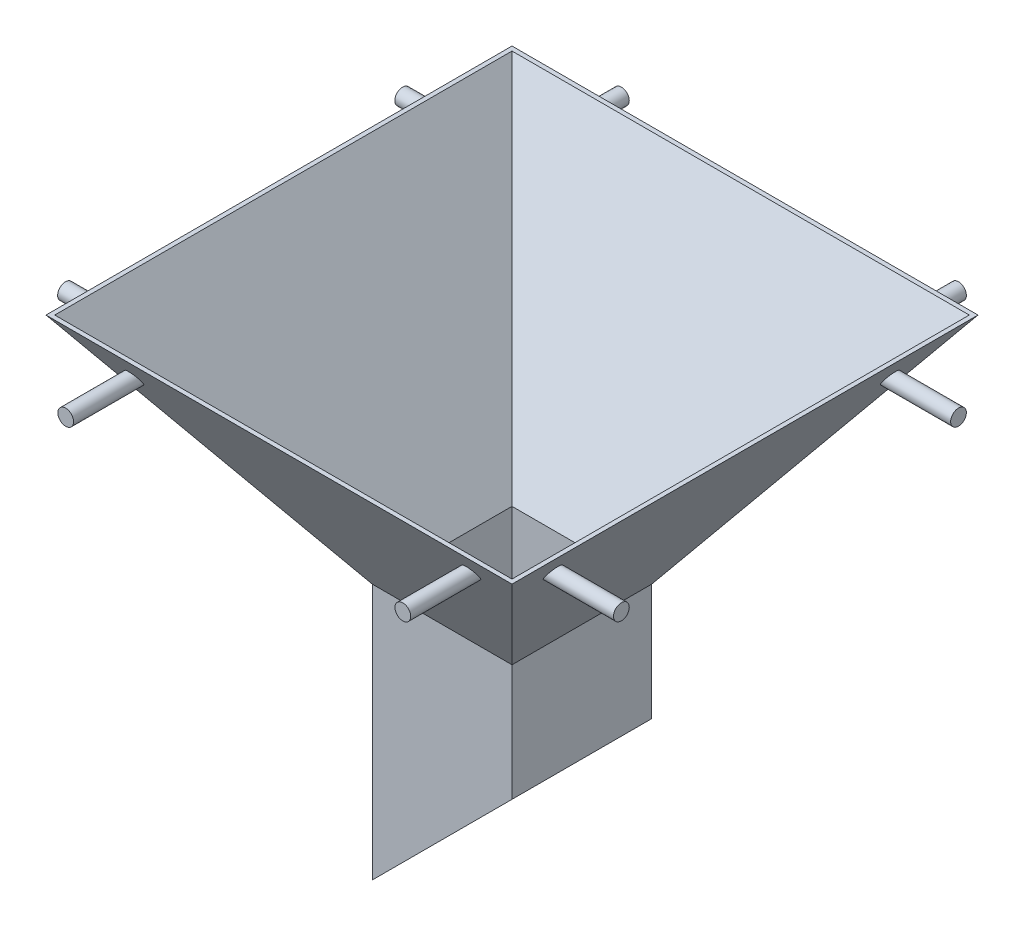
SolidWorks part; units mm, degrees
ref_plane "Alzado" through (0, 0, 0) normal (0, 0, 1) x (1, 0, 0)
ref_plane "Planta" through (0, 0, 0) normal (0, 1, 0) x (1, 0, 0)
ref_plane "Vista lateral" through (0, 0, 0) normal (1, 0, 0) x (0, 0, -1)
sketch "Croquis2" plane through (0, 0, 0) normal (0, 1, 0) x (1, 0, 0)
  line L1 (0, 0) -> (414.7, 0)
  line L2 (0, 0) -> (0, 414.7)
  line L3 (0, 414.7) -> (414.7, 414.7)
  line L4 (414.7, 0) -> (414.7, 414.7)
  dimension "D1" = 414.7
ref_plane "Plano1" through (0, -207.4, 0) normal (0, 1, 0) x (1, 0, 0)
sketch "Croquis3" plane through (0, -207.4, 0) normal (0, 1, 0) x (1, 0, 0)
  line L0 (207.35, 414.7) -> (207.35, 0) construction
  line L1 (0, 414.7) -> (414.7, 414.7) construction
  line L2 (0, 0) -> (414.7, 0) construction
  line L3 (207.35, 0) -> (414.7, 207.35) construction
  line L4 (414.7, 0) -> (414.7, 414.7) construction
  line L5 (414.7, 207.35) -> (0, 207.35) construction
  line L6 (0, 0) -> (0, 414.7) construction
  line L8 (145.2, 269.5) -> (269.5, 269.5)
  line L9 (145.2, 269.5) -> (145.2, 145.2)
  line L10 (145.2, 145.2) -> (269.5, 145.2)
  line L11 (269.5, 269.5) -> (269.5, 145.2)
  line L12 (145.2, 269.5) -> (269.5, 145.2) construction
  line L13 (145.2, 145.2) -> (269.5, 269.5) construction
  point P12 (207.35, 207.35)
  dimension "D2" = 124.3
loft "Recubrir1" add profiles "Croquis2", "Croquis3" connector at (0, 0, -414.7) connector at (145.2, -207.4, -269.5)
sketch "Croquis4" plane through (0, -207.4, 0) normal (0, -1, 0) x (1, 0, 0)
  line L1 (145.2, -145.2) -> (269.5, -145.2)
  line L2 (145.2, -145.2) -> (145.2, -269.5)
  line L3 (145.2, -269.5) -> (269.5, -269.5)
  line L4 (269.5, -145.2) -> (269.5, -269.5)
  line L5 (145.2, -145.2) -> (269.5, -269.5) construction
  line L6 (145.2, -269.5) -> (269.5, -145.2) construction
  point P0 (207.35, -207.35)
extrude "Saliente-Extruir1" add sketch "Croquis4" along normal blind 103.7
sketch "Croquis5" plane through (0, 0, -145.2) normal (0, 0, 1) x (1, 0, 0)
  line L0 (145.2, -311.1) -> (145.2, -435.4)
  line L1 (145.2, -435.4) -> (269.5, -311.1)
  line L2 (269.5, -311.1) -> (145.2, -311.1) construction
  line L3 (145.2, -311.1) -> (269.5, -311.1)
  dimension "D1" = 124.3
  dimension "D2" = 45
extrude "Saliente-Extruir2" add sketch "Croquis5" against normal up to surface (124.3 mm away) up to face at (222.8875, -285.175, -269.5)
shell "Vaciado1" thickness 3.175 removed face at (207.35, 0, -207.35)
ref_plane "Plano2" through (0, 0, 0) normal (1, 0, 0) x (0, 0, -1)
sketch "Croquis6" plane through (0, 0, 0) normal (1, 0, 0) x (0, 0, -1)
  line L0 (250, -50) -> (250, -100) construction
  line L1 (414.7, 0) -> (0, 0) construction
  line L2 (414.7, 0) -> (414.7, 10.241) construction
  line L3 (550, -50) -> (-50, -50) construction
  line L4 (-50, -100) -> (550, -100) construction
  line L5 (250, -100) -> (357.35, -100) construction
  line L6 (357.35, -100) -> (357.35, -50) construction
  line L7 (414.7, 10.241) -> (0, 10.241) construction
  line L8 (0, 10.241) -> (0, 0) construction
  line L9 (207.35, 10.241) -> (207.35, -30) construction
  circle A0 centre (357.35, -30) radius 7
  circle A2 centre (57.35, -30) radius 7
  dimension "D1" = 14
  dimension "D2" = 30
  dimension "D3" = 150
extrude "Saliente-Extruir3" add sketch "Croquis6" along normal up to surface and the other way blind 40 up to face at (36.3, -51.85, -274.725)
ref_plane "Plano3" through (0, 0, 0) normal (0, 0, 1) x (1, 0, 0)
sketch "Croquis7" plane through (0, 0, 0) normal (0, 0, 1) x (1, 0, 0)
  line L0 (0, 0) -> (0, 19.7266) construction
  line L1 (0, -228.085) -> (0, 228.085) construction
  line L2 (0, 19.7266) -> (415.0782, 19.7266) construction
  line L3 (415.0782, 19.7266) -> (414.7, 0) construction
  line L4 (207.5391, 19.7266) -> (207.5391, -72.7788) construction
  line L5 (0, 0) -> (414.7, 0) construction
  circle A0 centre (57.5391, -30) radius 7
  circle A1 centre (357.5391, -30) radius 7
  dimension "D1" = 14
  dimension "D2" = 30
  dimension "D3" = 150
extrude "Saliente-Extruir4" add sketch "Croquis7" along normal blind 40 and the other way up to surface other way up to face at (139.975, -51.85, -36.3)
ref_plane "Plano4" through (414.7, 0, 0) normal (1, 0, 0) x (0, 0, -1)
sketch "Croquis8" plane through (414.7, 0, 0) normal (1, 0, 0) x (0, 0, -1)
  line L0 (0, 0) -> (0, 56.09) construction
  line L1 (0, 56.09) -> (414.7, 56.09) construction
  line L2 (414.7, 56.09) -> (414.7, 0) construction
  line L3 (207.35, 56.09) -> (207.35, -57.8935) construction
  line L4 (0, 0) -> (414.7, 0) construction
  circle A0 centre (57.35, -30) radius 7
  circle A1 centre (357.35, -30) radius 7
  dimension "D1" = 14
  dimension "D2" = 30
  dimension "D3" = 150
extrude "Saliente-Extruir5" add sketch "Croquis8" along normal blind 40 and the other way up to surface other way up to face at (378.4, -51.85, -139.975)
ref_plane "Plano5" through (0, 0, -414.7) normal (0, 0, -1) x (-1, 0, 0)
sketch "Croquis9" plane through (0, 0, -414.7) normal (0, 0, -1) x (-1, 0, 0)
  line L0 (-414.7, 0) -> (-414.7, 56.09) construction
  line L1 (-414.7, 56.09) -> (0, 56.09) construction
  line L2 (0, 56.09) -> (0, 0) construction
  line L3 (-414.7, 0) -> (0, 0) construction
  line L4 (-207.35, 56.09) -> (-207.35, -89.7765) construction
  circle A0 centre (-357.35, -30) radius 7
  circle A1 centre (-57.35, -30) radius 7
  dimension "D1" = 14
  dimension "D2" = 30
  dimension "D3" = 150
extrude "Saliente-Extruir6" add sketch "Croquis9" along normal blind 40 and the other way up to surface other way up to face at (274.725, -51.85, -378.4)
sketch "Croquis10" plane through (0, -207.4, 0) normal (0, 1, 0) x (1, 0, 0)
  line L0 (266.325, 266.325) -> (148.375, 266.325) construction
  line L1 (148.375, 148.375) -> (266.325, 148.375)
  line L2 (148.375, 148.375) -> (148.375, 266.325)
  line L3 (148.375, 266.325) -> (266.325, 266.325)
  line L4 (266.325, 148.375) -> (266.325, 266.325)
  line L5 (266.325, 266.325) -> (148.375, 266.325) construction
extrude "Cortar-Extruir1" cut sketch "Croquis10" against normal blind 306
